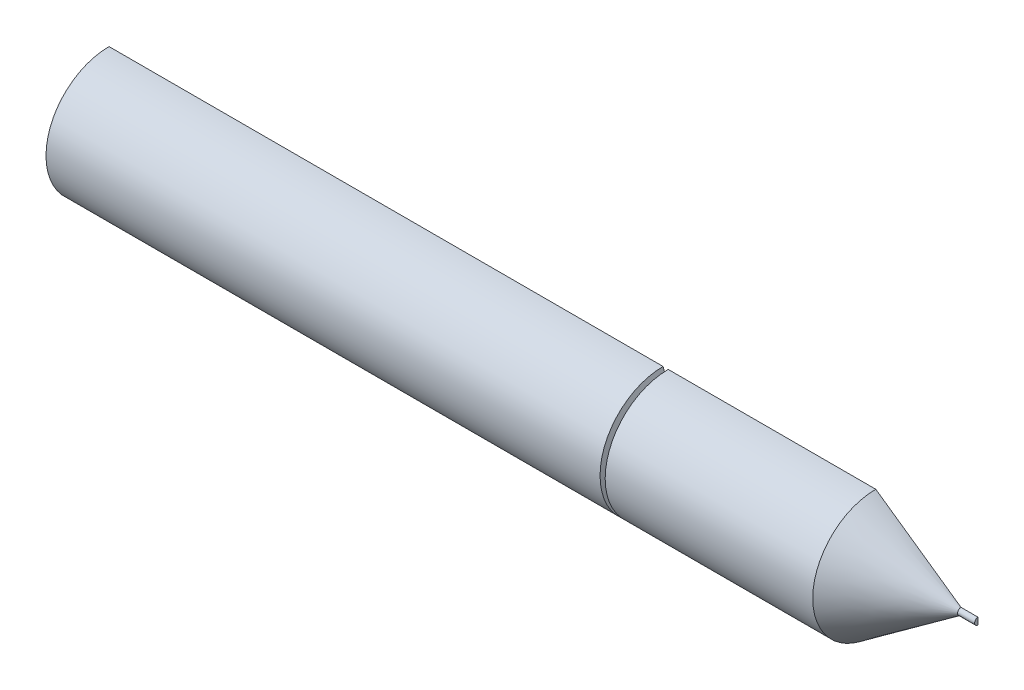
SolidWorks part; units mm, degrees
ref_plane "Front Plane" through (0, 0, 0) normal (0, 0, 1) x (1, 0, 0)
ref_plane "Top Plane" through (0, 0, 0) normal (0, 1, 0) x (1, 0, 0)
ref_plane "Right Plane" through (0, 0, 0) normal (1, 0, 0) x (0, 0, -1)
sketch "Sketch1" plane through (0, 0, 0) normal (0, 0, 1) x (1, 0, 0)
  line L1 (-315, 2) -> (-315, 37)
  line L3 (-315, 37) -> (135, 37)
  line L6 (-125, 0) -> (-325, 0)
  line L7 (-325, 0) -> (-325, 2)
  line L8 (-325, 2) -> (-315, 2)
  line L9 (-125, 0) -> (225, 0) construction
  line L10 (135, 37) -> (184.9852, 2)
  line L11 (184.9852, 2) -> (194.9852, 2)
  line L12 (194.9852, 2) -> (194.9852, 0)
  line L13 (194.9852, 0) -> (-125, 0)
  point P1 (0, 0)
  point P3 (0, 0)
  dimension "D1" = 10
  dimension "D2" = 450
  dimension "D3" = 145
  dimension "D4" = 2
  dimension "D5" = 35
  dimension "D6" = 2
  dimension "D7" = 10
revolve "Revolve1" add sketch "Sketch1" angle 360 about L9
sketch "Sketch4" plane through (0, 0, 0) normal (0, 1, 0) x (1, 0, 0)
  line L0 (23, 0) -> (23, 10)
  line L1 (23, 10) -> (13.1728, 37)
  line L2 (135, 37) -> (-315, 37) construction
  line L3 (20, 0) -> (20, 10)
  line L4 (20, 10) -> (10.1728, 37)
  line L5 (10.1728, 37) -> (13.1728, 37)
  line L6 (20, 0) -> (23, 0)
  dimension "D1" = 10
  dimension "D2" = 0
  dimension "D3" = 160
  dimension "D4" = 160
  dimension "D5" = 3
  dimension "D6" = 10
  dimension "D7" = 20
revolve "Revolve2" add sketch "Sketch4" angle 360 about L6
sketch "Sketch5" plane through (20, 0, 0) normal (-1, 0, 0) x (0, 0, 1)
  circle A0 centre (0, 0) radius 0.5
  point P19 (0, 0)
  dimension "D2" = 1
extrude "Cut-Extrude1" cut sketch "Sketch5" against normal blind 10
combine bodies "Combine1" operation type subtract main body 101 bodies to subtract 104
sketch "Sketch6" plane through (0, 0, 0) normal (0, 0, 1) x (1, 0, 0)
  line L0 (-351.8148, -78.9316) -> (351.8148, -78.9316)
  line L1 (-351.8148, -78.9316) -> (-351.8148, 78.9316)
  line L2 (351.8148, -78.9316) -> (351.8148, 78.9316)
  line L3 (-351.8148, 78.9316) -> (351.8148, 78.9316)
  line L4 (-351.8148, -78.9316) -> (351.8148, 78.9316) construction
  line L5 (351.8148, -78.9316) -> (-351.8148, 78.9316) construction
  point P1 (0, 0)
extrude "Cut-Extrude2" cut sketch "Sketch6" against normal blind 90
